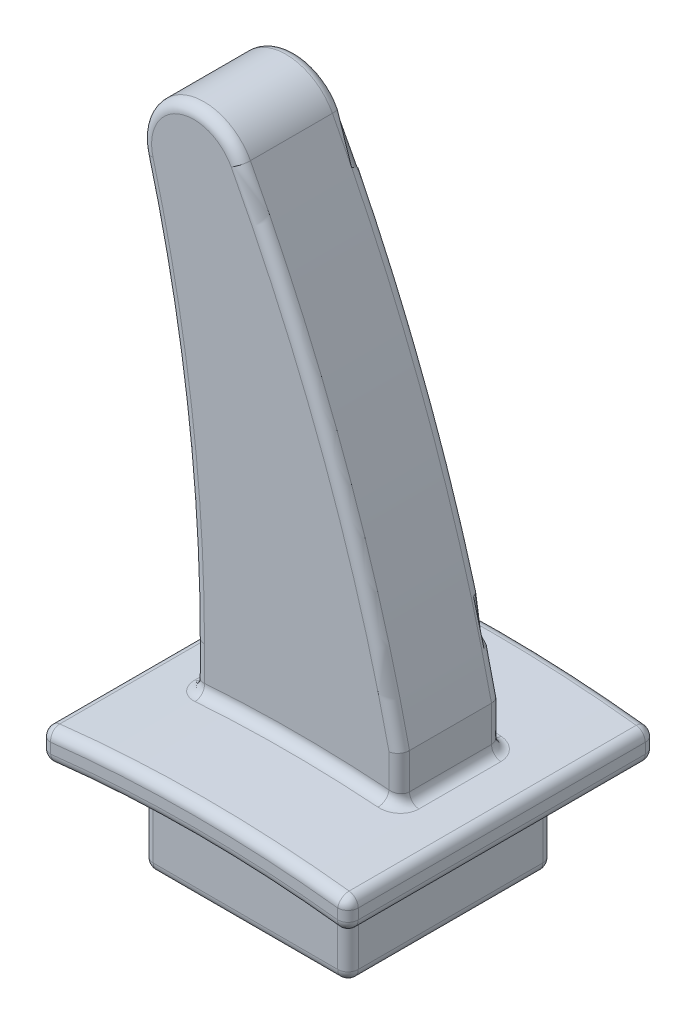
SolidWorks part; units mm, degrees
ref_plane "前视基准面" through (0, 0, 0) normal (0, 0, 1) x (1, 0, 0)
ref_plane "上视基准面" through (0, 0, 0) normal (0, 1, 0) x (1, 0, 0)
ref_plane "右视基准面" through (0, 0, 0) normal (1, 0, 0) x (0, 0, -1)
other "Configuration Table"
sketch "草图1" plane through (0, 0, 0) normal (0, 0, 1) x (1, 0, 0)
  line L4 (15, 119.0588) -> (15, 122.0819)
  line L6 (-15, 119.0588) -> (-15, 122.0819)
  line L7 (0, -55) -> (0, 55) construction
  arc A2 (15, 119.0588) -> (-15, 119.0588) centre (0, 0) ccw
  arc A3 (15, 122.0819) -> (-15, 122.0819) centre (0, 0) ccw
  dimension "D1" = 123
  dimension "D2" = 120
  dimension "D3" = 15
  dimension "D4" = 15
extrude "凸台-拉伸1" add sketch "草图1" along normal blind 15 and the other way blind 15
ref_plane "基准面1" through (0, 110, 0) normal (0, 1, 0) x (1, 0, 0)
sketch "草图2" plane through (0, 110, 0) normal (0, 1, 0) x (1, 0, 0)
  line L0 (-2.1677, 0) -> (2.1677, 0) construction
  line L1 (-10, 10) -> (10, 10)
  line L2 (-10, 10) -> (-10, -10)
  line L3 (-10, -10) -> (10, -10)
  line L4 (10, 10) -> (10, -10)
  line L5 (0, -2.1677) -> (0, 2.1677) construction
  dimension "D1" = 20
  dimension "D2" = 20
  dimension "D3" = 10
  dimension "D4" = 10
extrude "凸台-拉伸2" add sketch "草图2" along normal blind 12
sketch "草图3" plane through (0, 0, 0) normal (0, 0, 1) x (1, 0, 0)
  line L0 (0, -7.15) -> (0, 7.15) construction
  line L1 (-10, 122) -> (10, 122)
  line L2 (-10, 122) -> (-10, 127)
  line L4 (10, 122) -> (10, 127)
  line L5 (16.5, 110) -> (-16.5, 110) construction
  arc A3 (-10, 127) -> (-14.9892, 165.365) centre (-160, 127) ccw
  arc A4 (10, 127) -> (-5.5173, 169.0757) centre (-152.8895, 90.8264) ccw
  arc A5 (-5.5173, 169.0757) -> (-14.9892, 165.365) centre (-10.0394, 166.6746) ccw
  dimension "D4" = 150
  dimension "D5" = 166.8578
  dimension "D7" = 5.1201
  dimension "D1" = 20
  dimension "D2" = 10
  dimension "D3" = 12
  dimension "D6" = 5
  dimension "D8" = 5
  dimension "D9" = 38.365
extrude "凸台-拉伸3" add sketch "草图3" along normal blind 5 and the other way blind 5
fillet "圆角2" radius 1 24 edges at (-10, 110, 0) (-15, 120.5704, -15) (-10, 119.5826, 0) (-10, 114.7913, -10) (0, 123, -15) (15, 120.5704, -15) (0, 120, -15) (0, 120, -10) (0, 110, -10) (10, 114.7913, -10) (0, 120, 10) (10, 119.5826, 0) (10, 110, 0) (0, 110, 10) (-10, 114.7913, 10) (10, 114.7913, 10) (15, 119.0588, 0) (15, 122.0819, 0) (15, 120.5704, 15) (-15, 120.5704, 15) (0, 120, 15) (-15, 119.0588, 0) (-15, 122.0819, 0) (0, 123, 15)
sketch "草图4" plane through (0, 110, 0) normal (0, -1, 0) x (-1, 0, 0)
  point P0 (-5, 5)
  dimension "D1" = 5
  dimension "D2" = 5
fillet "圆角4" radius 1 14 edges at (-10, 122.5928, 0) (-10, 124.7964, -5) (0, 123, -5) (-11.2525, 146.344, -5) (-11.907, 171.4419, -5) (3.6614, 148.5615, -5) (10, 124.7964, -5) (10, 122.5928, 0) (10, 124.7964, 5) (0, 123, 5) (-10, 124.7964, 5) (-11.2525, 146.344, 5) (-11.907, 171.4419, 5) (3.6614, 148.5615, 5)
sketch "草图5" plane through (0, 110, 0) normal (0, -1, 0) x (1, 0, 0)
  line L1 (-8, 8) -> (8, 8)
  line L2 (-8, 8) -> (-8, -8)
  line L3 (-8, -8) -> (8, -8)
  line L4 (8, 8) -> (8, -8)
  dimension "D1" = 16
  dimension "D2" = 16
  dimension "D3" = 8
  dimension "D4" = 8
extrude "切除-拉伸1" cut sketch "草图5" against normal blind 8
fillet "圆角5" radius 1 12 edges at (-8, 114, -8) (8, 114, 8) (8, 110, 0) (8, 118, 0) (8, 114, -8) (0, 118, -8) (0, 110, -8) (0, 118, 8) (0, 110, 8) (-8, 110, 0) (-8, 114, 8) (-8, 118, 0)
